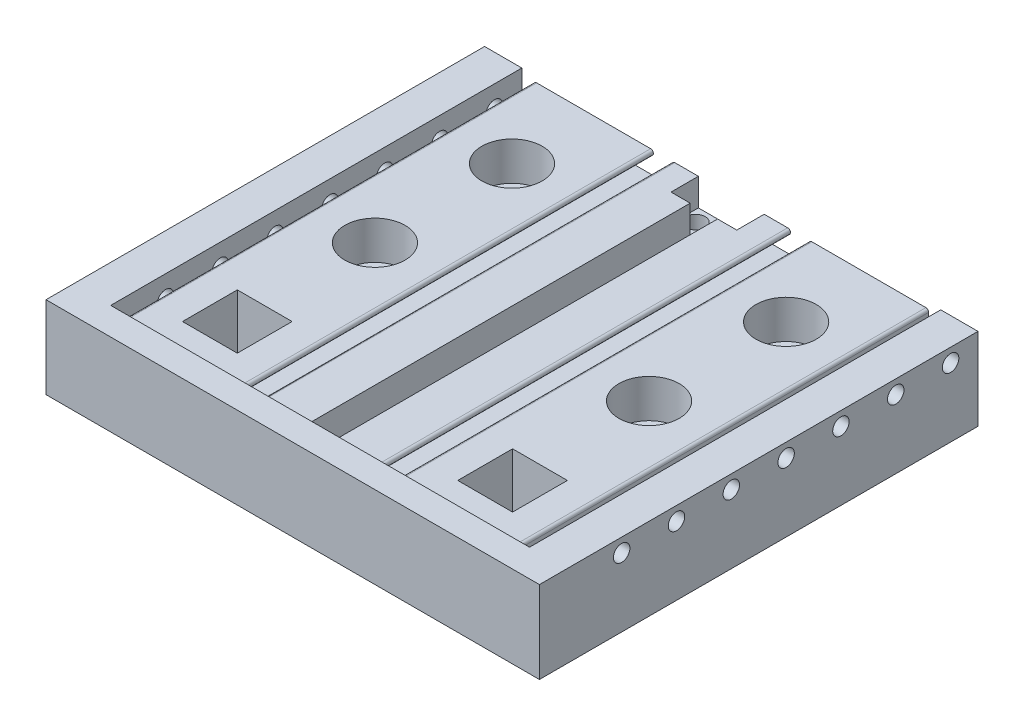
SolidWorks part; units mm, degrees
ref_plane "Front Plane" through (0, 0, 0) normal (0, 0, 1) x (1, 0, 0)
ref_plane "Top Plane" through (0, 0, 0) normal (0, 1, 0) x (1, 0, 0)
ref_plane "Right Plane" through (0, 0, 0) normal (1, 0, 0) x (0, 0, -1)
sketch "Sketch1" plane through (0, 0, 0) normal (0, 1, 0) x (1, 0, 0)
  line L1 (-12.8623, 1.9673) -> (77.1377, 1.9673)
  line L2 (-12.8623, 1.9673) -> (-12.8623, -78.0327)
  line L3 (-12.8623, -78.0327) -> (77.1377, -78.0327)
  line L4 (77.1377, 1.9673) -> (77.1377, -78.0327)
  dimension "D1" = 90
  dimension "D2" = 80
extrude "Boss-Extrude1" add sketch "Sketch1" along normal blind 14
sketch "Sketch2" plane through (0, 14, 0) normal (0, 1, 0) x (1, 0, 0)
  line L0 (77.1377, -78.0327) -> (77.1377, 1.9673) construction
  line L1 (-12.8623, -78.0327) -> (77.1377, -78.0327)
  line L2 (-12.8623, -78.0327) -> (-12.8623, -73.0327)
  line L3 (-5.8623, -73.0327) -> (70.1377, -73.0327)
  line L4 (77.1377, -78.0327) -> (77.1377, -68.0327)
  line L7 (-5.8623, -73.0327) -> (-5.8623, 1.9673)
  line L8 (-5.8623, 1.9673) -> (-12.8623, 1.9673)
  line L9 (-12.8623, -73.0327) -> (-12.8623, 1.9673)
  line L11 (70.1377, -73.0327) -> (70.1377, 1.9673)
  line L12 (70.1377, 1.9673) -> (77.1377, 1.9673)
  line L13 (77.1377, -68.0327) -> (77.1377, 1.9673)
  dimension "D1" = 5
  dimension "D2" = 7
  dimension "D3" = 7
extrude "Boss-Extrude2" add sketch "Sketch2" along normal blind 1
sketch "Sketch3" plane through (0, 14, 0) normal (0, 1, 0) x (1, 0, 0)
  circle A0 centre (57.1377, -38.0327) radius 3.25
  circle A2 centre (7.1377, -38.0327) radius 3.25
  circle A3 centre (32.1377, -38.0327) radius 3.25 [skipped]
  circle A4 centre (7.1377, -13.0327) radius 3.25
  circle A5 centre (57.1377, -13.0327) radius 3.25
  dimension "D1" = 6.5
  dimension "D2" = 3
  dimension "D3" = 2
extrude "Cut-Extrude1" cut sketch "Sketch3" against normal through all
sketch "Sketch4" plane through (0, 14, 0) normal (0, 1, 0) x (1, 0, 0)
  circle A0 centre (7.1377, -38.0327) radius 5.5
  circle A2 centre (57.1377, -38.0327) radius 5.5
  circle A3 centre (32.1377, -38.0327) radius 5.5 [skipped]
  circle A4 centre (57.1377, -13.0327) radius 5.5
  circle A5 centre (7.1377, -13.0327) radius 5.5
  dimension "D1" = 11
  dimension "D2" = 3
  dimension "D3" = 2
extrude "Cut-Extrude2" cut sketch "Sketch4" against normal blind 7
sketch "Sketch5" plane through (0, 0, -1.9673) normal (0, 0, -1) x (-1, 0, 0)
  line L0 (-70.1377, 14) -> (5.8623, 14) construction
  line L1 (-45.6377, 14) -> (-43.6377, 14)
  line L2 (-45.6377, 14) -> (-49.6377, 10)
  line L3 (-49.6377, 10) -> (-39.6377, 10)
  line L4 (-43.6377, 14) -> (-39.6377, 10)
  line L5 (-32.1377, 0) -> (-32.1377, 15) construction
  line L6 (-77.1377, 0) -> (12.8623, 0) construction
  line L7 (-70.1377, 15) -> (5.8623, 15) construction
  line L8 (-14.6377, 10) -> (-24.6377, 10)
  line L9 (-20.6377, 14) -> (-24.6377, 10)
  line L10 (-18.6377, 14) -> (-20.6377, 14)
  line L11 (-18.6377, 14) -> (-14.6377, 10)
  line L12 (-70.1377, 8) -> (-68.1377, 8)
  line L13 (5.8623, 14) -> (3.8623, 14)
  line L14 (5.8623, 14) -> (5.8623, 8)
  line L15 (5.8623, 8) -> (3.8623, 8)
  line L16 (3.8623, 14) -> (3.8623, 8)
  line L17 (-68.1377, 14) -> (-68.1377, 8)
  line L18 (-70.1377, 14) -> (-68.1377, 14)
  line L19 (-70.1377, 14) -> (-70.1377, 8)
  line L20 (-70.1377, 14) -> (5.8623, 14) construction
  line L21 (-34.6377, 14) -> (-29.6377, 14)
  line L22 (-34.6377, 14) -> (-34.6377, 9)
  line L23 (-34.6377, 9) -> (-29.6377, 9)
  line L24 (-29.6377, 14) -> (-29.6377, 9)
  point P16 (-19.6377, 10)
  point P17 (-44.6377, 10)
  point P32 (0, 0)
  point P33 (0, 0)
  point P34 (0, 0)
  point P35 (-40.1755, 10)
  point P36 (-36.8886, 10)
  point P37 (-32.1377, 9)
  dimension "D1" = 4
  dimension "D2" = 45
  dimension "D3" = 225
  dimension "D4" = 10
  dimension "D5" = 25
  dimension "D6" = 6
  dimension "D7" = 2
  dimension "D8" = 5
  dimension "D9" = 5
extrude "Cut-Extrude3" cut sketch "Sketch5" against normal up to surface (75 mm away) up to face at (32.1377, 14.5, 73.0327)
fillet "Fillet2" radius 0.5 6 edges at (68.1377, 14, 35.5327) (45.6377, 14, 35.5327) (43.6377, 14, 35.5327) (20.6377, 14, 35.5327) (18.6377, 14, 35.5327) (-3.8623, 14, 35.5327)
sketch "Sketch6" plane through (77.1377, 0, 0) normal (1, 0, 0) x (0, 0, -1)
  line L0 (-78.0327, 15) -> (1.9673, 15) construction
  line L1 (1.9673, 15) -> (1.9673, 0) construction
  circle A0 centre (-3.0327, 12.5) radius 1.5
  circle A1 centre (-13.0327, 12.5) radius 1.5
  circle A2 centre (-23.0327, 12.5) radius 1.5
  circle A3 centre (-33.0327, 12.5) radius 1.5
  circle A4 centre (-43.0327, 12.5) radius 1.5
  circle A5 centre (-53.0327, 12.5) radius 1.5
  circle A6 centre (-63.0327, 12.5) radius 1.5
  dimension "D1" = 3
  dimension "D2" = 2.5
  dimension "D3" = 5
  dimension "D4" = 7
extrude "Cut-Extrude4" cut sketch "Sketch6" against normal up to surface (7 mm away) up to face at (70.1377, 11.5, 35.5327)
ref_axis "Axis1" through (32.1377, 0, -1.9673) along (0, -1, 0)
sketch "Sketch7" plane through (-12.8623, 0, 0) normal (-1, 0, 0) x (0, 0, 1)
  line L0 (-1.9673, 15) -> (-1.9673, 0) construction
  line L1 (-1.9673, 15) -> (78.0327, 15) construction
  circle A0 centre (3.0327, 11) radius 1.5
  circle A1 centre (13.0327, 11) radius 1.5
  circle A2 centre (23.0327, 11) radius 1.5
  circle A3 centre (33.0327, 11) radius 1.5
  circle A4 centre (43.0327, 11) radius 1.5
  circle A5 centre (53.0327, 11) radius 1.5
  circle A6 centre (63.0327, 11) radius 1.5
  dimension "D1" = 3
  dimension "D2" = 5
  dimension "D3" = 4
  dimension "D4" = 7
extrude "Cut-Extrude5" cut sketch "Sketch7" against normal up to surface (7 mm away) up to face at (-5.8623, 11.5, 35.5327)
sketch "Sketch8" plane through (0, 0, -1.9673) normal (0, 0, -1) x (-1, 0, 0)
  line L0 (-42.4306, 14) -> (-34.6377, 14) construction
  line L1 (-38.1377, 14) -> (-26.1377, 14)
  line L2 (-38.1377, 14) -> (-38.1377, 9)
  line L3 (-38.1377, 9) -> (-26.1377, 9)
  line L4 (-26.1377, 14) -> (-26.1377, 9)
  line L5 (-32.1377, 0) -> (-32.1377, -39.7373) construction
  line L6 (-34.6377, 9) -> (-29.6377, 9) construction
  point P8 (-32.1377, 9)
  dimension "D1" = 12
extrude "Cut-Extrude6" cut sketch "Sketch8" against normal blind 5
sketch "Sketch9" plane through (0, 9, 0) normal (0, 1, 0) x (1, 0, 0)
  line L0 (32.1377, 1.9673) -> (32.1377, -3.2829) construction
  line L1 (38.1377, 1.9673) -> (26.1377, 1.9673) construction
  line L2 (38.1377, -3.0327) -> (38.1377, 1.9673) construction
  circle A0 centre (36.1377, -0.5327) radius 1.75
  circle A1 centre (28.1377, -0.5327) radius 1.75
  point P11 (38.1377, -0.5327)
  dimension "D1" = 3.5
  dimension "D2" = 2
extrude "Cut-Extrude7" cut sketch "Sketch9" against normal through all
sketch "Sketch10" plane through (0, 0, 0) normal (0, -1, 0) x (1, 0, 0)
  circle A0 centre (36.1377, 0.5327) radius 3
  circle A2 centre (28.1377, 0.5327) radius 3.25
  dimension "D1" = 6
  dimension "D2" = 6.5
extrude "Cut-Extrude8" cut sketch "Sketch10" against normal blind 4
other "Move Face1" flip direction yes face at (70.1377, 12.5, 1.5327) face at (-5.8623, 11, 4.5327) offset 0.2 parameters "D1"=0.2
sketch "Sketch11" plane through (0, 14, 0) normal (0, 1, 0) x (1, 0, 0)
  line L0 (17.4306, -73.0327) -> (-3.3623, -73.0327) construction
  line L1 (2.0342, -68.0327) -> (12.0342, -68.0327)
  line L2 (2.0342, -68.0327) -> (2.0342, -58.0327)
  line L3 (2.0342, -58.0327) -> (12.0342, -58.0327)
  line L4 (12.0342, -68.0327) -> (12.0342, -58.0327)
  line L5 (32.1377, -69.8195) -> (32.1377, -53.1374) construction
  line L6 (70.3377, -73.0327) -> (-6.0623, -73.0327) construction
  line L8 (52.2413, -68.0327) -> (52.2413, -58.0327)
  line L9 (62.2413, -58.0327) -> (52.2413, -58.0327)
  line L10 (62.2413, -68.0327) -> (62.2413, -58.0327)
  line L11 (62.2413, -68.0327) -> (52.2413, -68.0327)
  point P6 (7.0342, -73.0327)
  point P7 (7.0342, -68.0327)
  point P10 (0, 0)
  point P13 (32.1377, -73.0327)
  dimension "D1" = 10
  dimension "D2" = 10
  dimension "D3" = 5
extrude "Cut-Extrude10" cut sketch "Sketch11" against normal through all
